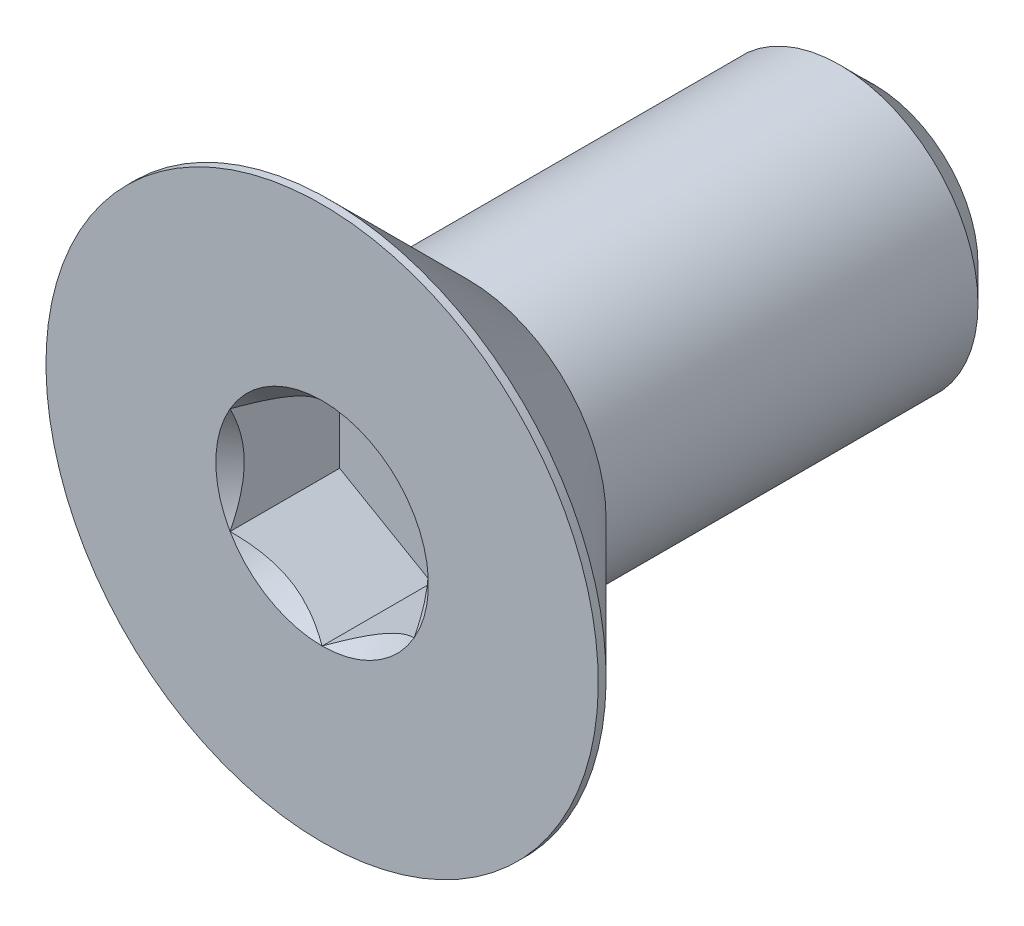
SolidWorks part; units mm, degrees
ref_plane "Front" through (0, 0, 0) normal (0, 0, 1) x (1, 0, 0)
ref_plane "Top" through (0, 0, 0) normal (0, 1, 0) x (1, 0, 0)
ref_plane "Right" through (0, 0, 0) normal (1, 0, 0) x (0, 0, -1)
sketch "Sketch11" plane through (0, 0, 0) normal (1, 0, 0) x (0, 0, -1)
  line L0 (-3, 3) -> (3, 3) construction
  line L5 (-3, 3) -> (-3, -3) construction
  line L6 (3, 1.5) -> (3, -1.5) construction
  line L7 (-2.99, 1) -> (-2.99, -1) construction
  line L8 (2.9688, 1.5541) -> (3.4688, 1.5541) construction
  line L9 (3.4688, 1.5541) -> (3.2188, 1.1211) construction
  line L10 (3.2188, 1.1211) -> (2.9688, 1.5541) construction
  line L11 (3.1875, 1.1752) -> (3.25, 1.1752) construction
  line L12 (3.2188, 1.1752) -> (3.2188, 1.1211) construction
  line L13 (2.9844, 1.5271) -> (3.4531, 1.5271) construction
  line L14 (3.2188, 1.5541) -> (3.2188, 1.5) construction
  line L15 (3, 1.5) -> (3.4375, 1.5) construction
  line L17 (-2.915, 3) -> (0.085, 0) construction
  line L18 (0.085, 0) -> (-2.915, -3) construction
  point P3 (-1.3, 3)
  point P8 (0, 3)
  point P21 (3.2188, 1.5271)
  point P26 (-3, 0)
  point P28 (-2.99, 0)
  point P29 (3, 0)
  dimension "Length" = 6
  dimension "Head Diameter" = 6
  dimension "Thread Major Diameter" = 3
  dimension "Head Height" = 1.7
  dimension "Drive Size" = 2
  dimension "Thread Pitch" = 0.5
  dimension "D1" = 0.0625
  dimension "D2" = 0.01
  dimension "D3" = 0.085
  dimension "Countersink Angle" = 90
sketch "Sketch1" plane through (0, 0, 0) normal (1, 0, 0) x (0, 0, -1)
  line L2 (-1.3, 1.5) -> (3, 1.5)
  line L3 (3, 1.5) -> (3, 0)
  line L4 (-1.81, 1.5) -> (-1.81, 0)
  line L5 (-1.3, 1.5) -> (-1.81, 1.5)
  line L6 (-3, 3) -> (-3, -3) construction
  line L7 (3, 1.5) -> (3, -1.5) construction
  line L8 (-1.81, 0) -> (3, 0)
  dimension "D1" = 1.19
revolve "Revolve1" add sketch "Sketch1" angle 360 mid plane about L8
chamfer "Chamfer1" distance 0.375 angle 45 1 edges at (0, -1.5, -3)
sketch "Sketch7" plane through (0, 0, 0) normal (1, 0, 0) x (0, 0, -1)
  line L2 (-3, 3) -> (-2.915, 3)
  line L5 (-1.3, 1.385) -> (-1.3, 0)
  line L6 (-3, 3) -> (-3, 0)
  line L8 (-3, 3) -> (-3, -3) construction
  line L9 (-3, 0) -> (-1.3, 0)
  line L12 (-2.915, 3) -> (-1.3, 1.385)
  line L13 (-2.915, 3) -> (0.085, 0) construction
revolve "Revolve2" add sketch "Sketch7" angle 360 mid plane about L9 region at (0, 1.1696, 2.2571)
ref_plane "Plane1" through (0, 0, 1.3) normal (0, 0, 1) x (1, 0, 0)
sketch "Sketch5" plane through (0, 0, 3) normal (0, 0, 1) x (1, 0, 0)
  line L1 (1, -0.5774) -> (1, 0.5774)
  line L2 (1, 0.5774) -> (0, 1.1547)
  line L3 (0, 1.1547) -> (-1, 0.5774)
  line L4 (-1, 0.5774) -> (-1, -0.5774)
  line L5 (-1, -0.5774) -> (0, -1.1547)
  line L6 (0, -1.1547) -> (1, -0.5774)
  circle A0 centre (0, 0) radius 1 construction
extrude "Cut-Extrude2" cut sketch "Sketch5" against normal blind 1.19
sketch "Sketch6" plane through (0, 0, 3) normal (0, 0, -1) x (-1, 0, 0)
  circle A0 centre (0, 0) radius 1.1547
extrude "Cut-Extrude3" cut sketch "Sketch6" along normal blind 1.19 draft 45
sketch "Sketch12" [suppressed] plane through (0, 0, -3) normal (0, 0, -1) x (-1, 0, 0)
  circle A0 centre (0, 0) radius 1.5 construction
  circle A1 centre (0, 0) radius 1.5
curve "Helix/Spiral1" [suppressed] pitch 0.5 height 6 turns 12
sketch "Sketch13" [suppressed] plane through (0, 0, 0) normal (1, 0, 0) x (0, 0, -1)
  line L0 (2.9844, 1.5271) -> (3.4531, 1.5271)
  line L1 (3.4531, 1.5271) -> (3.25, 1.1752)
  line L2 (3.25, 1.1752) -> (3.1875, 1.1752)
  line L3 (3.1875, 1.1752) -> (2.9844, 1.5271)
sweep "Cut-Sweep1" [suppressed] cut profiles "Sketch13" path "Helix/Spiral1"
combine bodies "Combine1" operation type add bodies to combine 113 108
equation "\"D1@Chamfer1\"=\"Thread Pitch@Sketch11\" * .75"
equation "\"D1@Cut-Extrude2\"= \"Head Height@Sketch11\" * .7"
equation "\"D1@Cut-Extrude3\" = \"D1@Cut-Extrude2\""
equation "\"D1@Sketch11\"=\"Thread Pitch@Sketch11\"/8"
equation "\"D3@Sketch11\"=\"Head Height@Sketch11\"*.05"
equation "\"D4@Helix/Spiral1\"=\"Thread Pitch@Sketch11\""
equation "\"D1@Sketch1\"=\"Head Height@Sketch11\"*.7"
equation "\"D3@Helix/Spiral1\"=\"Length@Sketch11\""
